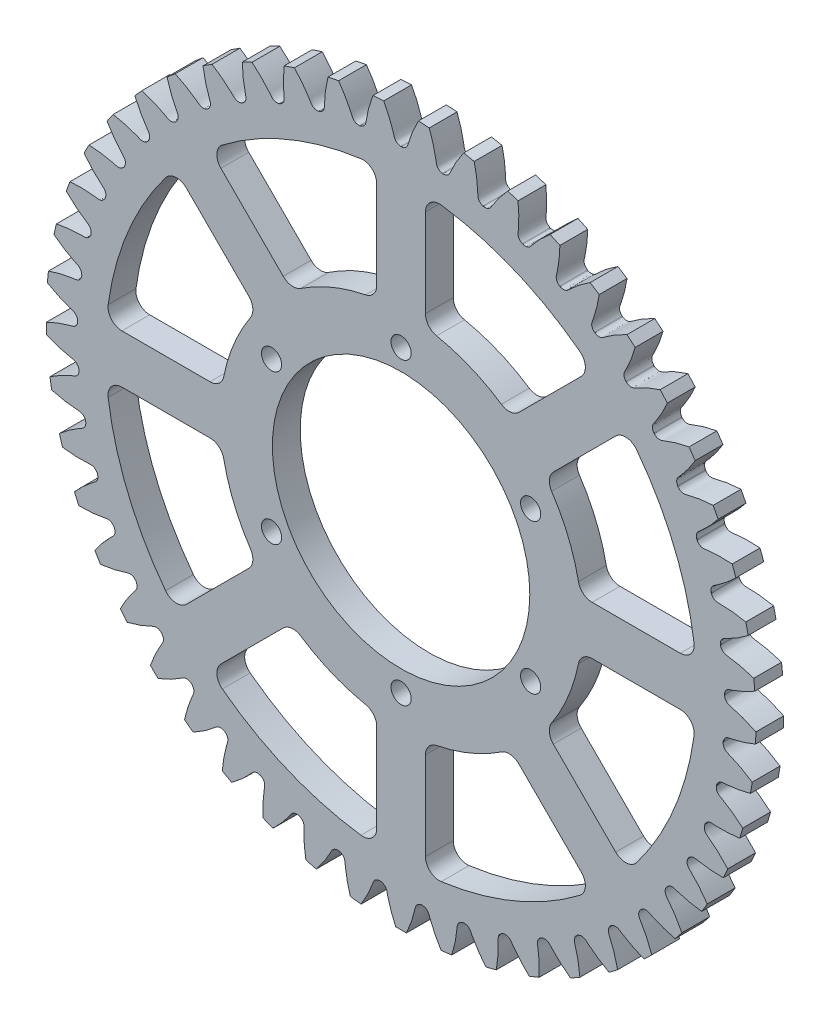
SolidWorks part; units mm, degrees
material "A-玻璃纤维"
ref_plane "前视基准面" through (0, 0, 0) normal (0, 0, 1) x (1, 0, 0)
ref_plane "上视基准面" through (0, 0, 0) normal (0, 1, 0) x (1, 0, 0)
ref_plane "右视基准面" through (0, 0, 0) normal (1, 0, 0) x (0, 0, -1)
other "Configuration Table"
sketch "草图1" plane through (0, 0, 0) normal (0, 0, 1) x (1, 0, 0)
  circle A0 centre (0, 0) radius 51
extrude "凸台-拉伸1" add sketch "草图1" along normal blind 4
ref_axis "基准轴1" through (0, 0, -0.25) along (0, 0, 1)
sketch "草图2" plane through (0, 0, 0) normal (0, 0, 1) x (1, 0, 0)
  line L0 (0, 0) -> (0, 51) construction
  circle A0 centre (0, 0) radius 51 construction
  arc A1 (0.0501, 46.5) -> (-0.0501, 46.5) centre (0, 0) ccw
  arc A2 (8.0317, 58.0483) -> (-8.0317, 58.0483) centre (0, 0) ccw
  spline S0 degree 3 poles (0.0501, 46.5) (0.8731, 46.6035) (0.9763, 47.2232) (1.1838, 47.8983) (1.2684, 48.1588) (1.3644, 48.4347) (1.4723, 48.726) (1.5927, 49.0321) (1.7263, 49.3528) (1.8736, 49.6877) (2.0355, 50.0362) (2.2123, 50.398) (2.4047, 50.7726) (2.6134, 51.1594) (2.8388, 51.558) (3.0815, 51.9679) (3.342, 52.3885) (3.6209, 52.8193) (3.9187, 53.2597) (4.2359, 53.7091) (4.5729, 54.1669) (4.9302, 54.6325) (5.3082, 55.1052) (5.7074, 55.5844) (6.1282, 56.0695) (6.5709, 56.5597) (7.1994, 57.2282) (7.6924, 57.7216) (8.0317, 58.0483) knots 0 0 0 0 0.111956 0.129916 0.149172 0.169724 0.191571 0.214714 0.239152 0.264886 0.291916 0.320241 0.349862 0.380779 0.412991 0.446499 0.481302 0.517401 0.554795 0.593486 0.633471 0.674753 0.71733 0.761203 0.806371 0.852835 0.900594 1 1 1 1
  spline S1 degree 3 poles (-0.0501, 46.5) (-0.8731, 46.6035) (-0.9763, 47.2232) (-1.1838, 47.8983) (-1.2684, 48.1588) (-1.3644, 48.4347) (-1.4723, 48.726) (-1.5927, 49.0321) (-1.7263, 49.3528) (-1.8736, 49.6877) (-2.0355, 50.0362) (-2.2123, 50.398) (-2.4047, 50.7726) (-2.6134, 51.1594) (-2.8388, 51.558) (-3.0815, 51.9679) (-3.342, 52.3885) (-3.6209, 52.8193) (-3.9187, 53.2597) (-4.2359, 53.7091) (-4.5729, 54.1669) (-4.9302, 54.6325) (-5.3082, 55.1052) (-5.7074, 55.5844) (-6.1282, 56.0695) (-6.5709, 56.5597) (-7.1994, 57.2282) (-7.6924, 57.7216) (-8.0317, 58.0483) knots 0 0 0 0 0.111956 0.129916 0.149172 0.169724 0.191571 0.214714 0.239152 0.264886 0.291916 0.320241 0.349862 0.380779 0.412991 0.446499 0.481302 0.517401 0.554795 0.593486 0.633471 0.674753 0.71733 0.761203 0.806371 0.852835 0.900594 1 1 1 1
extrude "切除-拉伸1" cut sketch "草图2" along normal through all
pattern_circular "阵列(圆周)1" count 49 every 7.347 about axis through (0, 0, -0.25) along (0, 0, 1) of "切除-拉伸1"
sketch "草图3" plane through (0, 0, 0) normal (0, 0, 1) x (1, 0, 0)
  circle A0 centre (0, 0) radius 49 construction
  dimension "Dn" = 98
sketch "草图4" plane through (0, 0, 4) normal (0, 0, 1) x (1, 0, 0)
  circle A0 centre (18.6195, 10.75) radius 1.45
  circle A1 centre (0, 0) radius 21.5 construction
  circle A2 centre (0, 21.5) radius 1.45
  circle A6 centre (18.6195, -10.75) radius 1.45
  circle A7 centre (0, -21.5) radius 1.45
  circle A8 centre (-18.6195, -10.75) radius 1.45
  circle A9 centre (-18.6195, 10.75) radius 1.45
  circle A10 centre (0, 0) radius 18.5
  dimension "D1" = 43
  dimension "D2" = 2.9
  dimension "D4" = 37
  dimension "D3" = 6
extrude "切除-拉伸2" cut sketch "草图4" against normal through all
sketch "草图5" plane through (0, 0, 4) normal (0, 0, 1) x (1, 0, 0)
  line L0 (0, 0) -> (-42.5, 0) construction
  line L1 (0, 0) -> (-30.052, 30.052) construction
  line L2 (-25.7633, 3.5) -> (-42.3556, 3.5)
  line L3 (-32.4248, 27.4751) -> (-20.6923, 15.7426)
  line L4 (-3.5, 42.3556) -> (-3.5, 25.7633)
  line L5 (-15.7426, 20.6923) -> (-27.4751, 32.4248)
  line L6 (27.4751, 32.4248) -> (15.7426, 20.6923)
  line L7 (3.5, 25.7633) -> (3.5, 42.3556)
  line L8 (42.3556, 3.5) -> (25.7633, 3.5)
  line L9 (20.6923, 15.7426) -> (32.4248, 27.4751)
  line L10 (32.4248, -27.4751) -> (20.6923, -15.7426)
  line L11 (25.7633, -3.5) -> (42.3556, -3.5)
  line L12 (3.5, -42.3556) -> (3.5, -25.7633)
  line L13 (15.7426, -20.6923) -> (27.4751, -32.4248)
  line L14 (-27.4751, -32.4248) -> (-15.7426, -20.6923)
  line L15 (-3.5, -25.7633) -> (-3.5, -42.3556)
  line L16 (-42.3556, -3.5) -> (-25.7633, -3.5)
  line L17 (-20.6923, -15.7426) -> (-32.4248, -27.4751)
  line L18 (0, 0) -> (-20.6923, 15.7426) construction
  circle A0 centre (0, 0) radius 26 construction
  circle A1 centre (0, 0) radius 42.5 construction
  arc A2 (-32.4248, 27.4751) -> (-42.3556, 3.5) centre (0, 0) ccw
  arc A3 (-25.7633, 3.5) -> (-20.6923, 15.7426) centre (0, 0) cw
  arc A4 (-15.7426, 20.6923) -> (-3.5, 25.7633) centre (0, 0) cw
  arc A5 (-3.5, 42.3556) -> (-27.4751, 32.4248) centre (0, 0) ccw
  arc A6 (3.5, 25.7633) -> (15.7426, 20.6923) centre (0, 0) cw
  arc A7 (27.4751, 32.4248) -> (3.5, 42.3556) centre (0, 0) ccw
  arc A8 (20.6923, 15.7426) -> (25.7633, 3.5) centre (0, 0) cw
  arc A9 (42.3556, 3.5) -> (32.4248, 27.4751) centre (0, 0) ccw
  arc A10 (25.7633, -3.5) -> (20.6923, -15.7426) centre (0, 0) cw
  arc A11 (32.4248, -27.4751) -> (42.3556, -3.5) centre (0, 0) ccw
  arc A12 (15.7426, -20.6923) -> (3.5, -25.7633) centre (0, 0) cw
  arc A13 (3.5, -42.3556) -> (27.4751, -32.4248) centre (0, 0) ccw
  arc A14 (-3.5, -25.7633) -> (-15.7426, -20.6923) centre (0, 0) cw
  arc A15 (-27.4751, -32.4248) -> (-3.5, -42.3556) centre (0, 0) ccw
  arc A16 (-20.6923, -15.7426) -> (-25.7633, -3.5) centre (0, 0) cw
  arc A17 (-42.3556, -3.5) -> (-32.4248, -27.4751) centre (0, 0) ccw
  dimension "D1" = 85
  dimension "D2" = 52
  dimension "D3" = 45
  dimension "D4" = 3.5
  dimension "D5" = 3.5
  dimension "D6" = 8
extrude "切除-拉伸3" cut sketch "草图5" against normal through all
fillet "圆角1" radius 2 32 edges at (-42.3556, 3.5, 2) (-32.4248, 27.4751, 2) (-20.6923, 15.7426, 2) (-25.7633, 3.5, 2) (27.4751, -32.4248, 2) (3.5, -42.3556, 2) (3.5, -25.7633, 2) (15.7426, -20.6923, 2) (-3.5, -42.3556, 2) (-27.4751, -32.4248, 2) (-15.7426, -20.6923, 2) (-3.5, -25.7633, 2) (-32.4248, -27.4751, 2) (-42.3556, -3.5, 2) (-25.7633, -3.5, 2) (-20.6923, -15.7426, 2) (-3.5, 25.7633, 2) (-15.7426, 20.6923, 2) (3.5, 42.3556, 2) (27.4751, 32.4248, 2) (15.7426, 20.6923, 2) (3.5, 25.7633, 2) (32.4248, 27.4751, 2) (42.3556, 3.5, 2) (25.7633, 3.5, 2) (20.6923, 15.7426, 2) (42.3556, -3.5, 2) (32.4248, -27.4751, 2) (20.6923, -15.7426, 2) (25.7633, -3.5, 2) (-3.5, 42.3556, 2) (-27.4751, 32.4248, 2)
